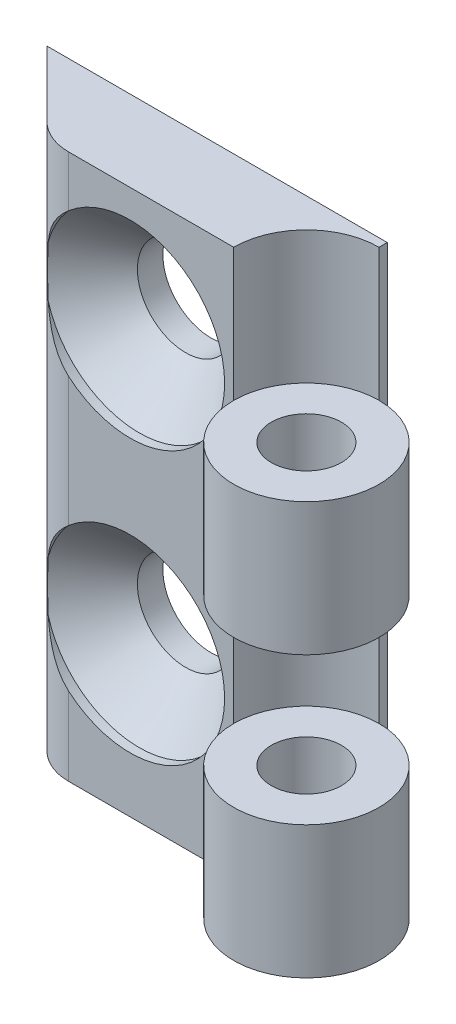
SolidWorks part; units mm, degrees
ref_plane "Front Plane" through (0, 0, 0) normal (0, 0, 1) x (1, 0, 0)
ref_plane "Top Plane" through (0, 0, 0) normal (0, 1, 0) x (1, 0, 0)
ref_plane "Right Plane" through (0, 0, 0) normal (1, 0, 0) x (0, 0, -1)
sketch "Sketch1" plane through (0, 0, 0) normal (0, 1, 0) x (1, 0, 0)
  line L0 (0, 4.45) -> (-18.73, 4.45)
  line L1 (-4, 0) -> (4, 0) construction
  line L2 (-13.082, 0) -> (-4, 0)
  line L4 (-15.1271, 0.8471) -> (-18.73, 4.45)
  line L6 (0, 4.45) -> (0, 4)
  arc A0 (-15.1271, 0.8471) -> (-13.082, 0) centre (-13.082, 2.8922) ccw
  circle A1 centre (0, 0) radius 1.93
  circle A2 centre (0, 0) radius 4
  dimension "D1" = 2.8922
  dimension "D2" = 8
  dimension "D6" = 3.86
  dimension "D3" = 4.45
  dimension "D4" = 18.73
  dimension "D5" = 0.45
extrude "Boss-Extrude1" add sketch "Sketch1" along normal blind 7.3 contours A2 L0 L2 | A2 L2 A1 | A2 A1 | L2 A2 A1 region at (-9.6523, 0, -2.4612) region at (2.7484, 0, -2.7484)
extrude "Boss-Extrude2" add sketch "Sketch1<3>" along normal blind 30 contours A2 L0 L2 region at (-9.6523, 0, -2.4612)
sketch "Sketch1<3>" plane through (0, 0, 0) normal (0, 1, 0) x (1, 0, 0) same geometry as "Sketch1"
extrude "Boss-Extrude5" add sketch "Sketch1<7>" along normal blind 7.3 from offset 15.4 contours L2 A2 A1 | A2 L2 A1 | A2 A1 region at (2.7484, 0, -2.7484)
sketch "Sketch1<7>" plane through (0, 0, 0) normal (0, 1, 0) x (1, 0, 0) same geometry as "Sketch1"
hole_wizard "CSK for M5 Countersunk Flat Head Screw1" positions "Sketch4" profile "Sketch3" countersink size "M5" standard "ISO" end condition through all
sketch "Sketch4" plane through (0, 0, 0) normal (0, 0, 1) x (1, 0, 0)
  line L2 (4, 15.4) -> (4, 22.7) construction
  point P0 (-9.7, 23.25)
  point P3 (-9.7, 8.25)
  dimension "D1" = 13.7
sketch "Sketch3" plane through (-9.7, 23.25, 0) normal (1, 0, 0) x (0, -1, 0)
  line L0 (0, 0) -> (0, 4.45)
  line L1 (0, 4.45) -> (2.65, 4.45)
  line L2 (2.65, 4.45) -> (2.65, 3.05)
  line L3 (2.65, 3.05) -> (5.2, 0.5)
  line L4 (5.2, 0.5) -> (5.2, 0)
  line L6 (5.2, 0) -> (0, 0)
  line L7 (-2.65, 3.05) -> (-5.2, 0.5) construction
  line L11 (0, -6.35) -> (0, 107.95) construction
  dimension "Thru Hole Dia." = 5.3
  dimension "Thru Hole Depth" = 4.45
  dimension "C'Sink Dia." = 10.4
  dimension "C'Sink Angle" = 90
  dimension "Head Clearance" = 0.5
equation "\"D4@Sketch1\"=22.73-(\"D2@Sketch1\"/2)"
equation "\"D5@Sketch1\"=20-(\"D2@Sketch1\"/2)"
